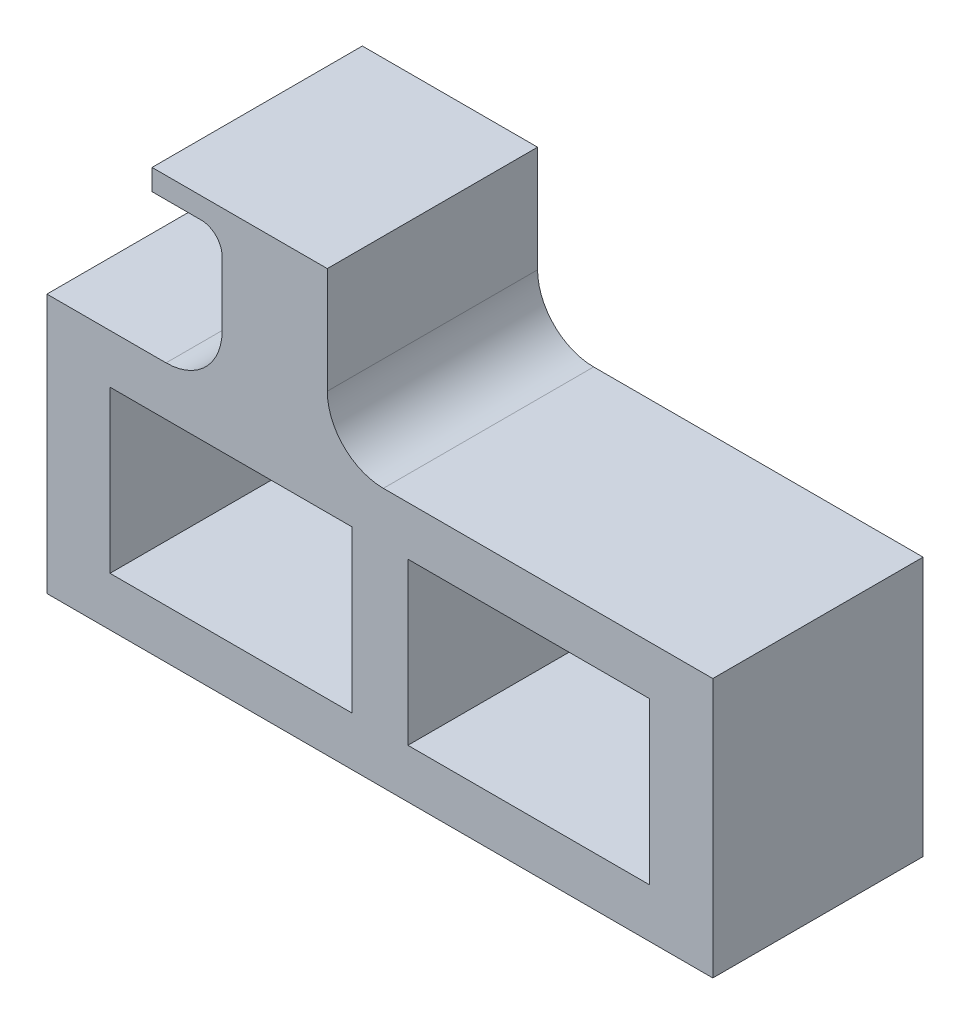
SolidWorks part; units mm, degrees
ref_plane "Front Plane" through (0, 0, 0) normal (0, 0, 1) x (1, 0, 0)
ref_plane "Top Plane" through (0, 0, 0) normal (0, 1, 0) x (1, 0, 0)
ref_plane "Right Plane" through (0, 0, 0) normal (1, 0, 0) x (0, 0, -1)
sketch "Sketch1" plane through (0, 0, 0) normal (0, 1, 0) x (1, 0, 0)
  line L1 (0, 0) -> (95, 0)
  line L2 (0, 0) -> (0, 30)
  line L3 (0, 30) -> (95, 30)
  line L4 (95, 0) -> (95, 30)
  dimension "D1" = 95
  dimension "D2" = 30
extrude "Boss-Extrude1" add sketch "Sketch1" along normal blind 7 contours L1 L4 L3 L2
sketch "Sketch2" plane through (0, 7, 0) normal (0, 1, 0) x (1, 0, 0)
  line L0 (0, 30) -> (95, 30) construction
  line L1 (0, 0) -> (9, 0)
  line L2 (0, 0) -> (0, 30)
  line L3 (0, 30) -> (9, 30)
  line L4 (9, 0) -> (9, 30)
  line L5 (47.5, 0) -> (47.5, 30) construction
  line L6 (0, 0) -> (95, 0) construction
  line L7 (51.5, 30) -> (51.5, 0)
  line L8 (51.5, 30) -> (43.5, 30)
  line L9 (47.5, 30) -> (47.5, 0)
  line L10 (51.5, 0) -> (43.5, 0)
  line L11 (43.5, 30) -> (43.5, 0)
  line L12 (95, 30) -> (86, 30)
  line L13 (95, 0) -> (86, 0)
  line L14 (95, 0) -> (95, 30)
  line L15 (86, 0) -> (86, 30)
  line M9 (0, 30) -> (0, 0)
  line M10 (0, 0) -> (95, 0)
  line M11 (95, 0) -> (95, 30)
  line M12 (95, 30) -> (0, 30)
  dimension "D1" = 9
  dimension "D2" = 4
extrude "Boss-Extrude2" add sketch "Sketch2" along normal blind 23 contours L4 M10 M12 M9 | L8 L11 L9 M10 | L9 L7 M12 M10 | L15 M10 M11 M12 region at (4.5, 7, -15) region at (45.5, 7, -15) region at (49.5, 7, -15) region at (90.5, 7, -15)
sketch "Sketch3" plane through (0, 30, 0) normal (0, 1, 0) x (1, 0, 0)
  line L1 (0, 0) -> (95, 0)
  line L2 (0, 0) -> (0, 30)
  line L3 (0, 30) -> (95, 30)
  line L4 (95, 0) -> (95, 30)
extrude "Boss-Extrude3" add sketch "Sketch3" along normal blind 7
sketch "Sketch4" plane through (0, 37, 0) normal (0, 1, 0) x (1, 0, 0)
  line L0 (0, 30) -> (0, 0) construction
  line L1 (25, 0) -> (40, 0)
  line L2 (25, 0) -> (25, 30)
  line L3 (25, 30) -> (40, 30)
  line L4 (40, 0) -> (40, 30)
  line L5 (0, 0) -> (95, 0) construction
  line L6 (95, 30) -> (0, 30) construction
  dimension "D1" = 25
  dimension "D2" = 15
extrude "Boss-Extrude4" add sketch "Sketch4" along normal blind 20.15
sketch "Sketch5" plane through (0, 57.15, 0) normal (0, 1, 0) x (1, 0, 0)
  line L0 (40, 0) -> (40, 30) construction
  line L1 (15, 30) -> (40, 30)
  line L2 (15, 30) -> (15, 0)
  line L3 (15, 0) -> (40, 0)
  line L4 (40, 30) -> (40, 0)
  line L5 (25, 0) -> (40, 0) construction
  line L6 (40, 30) -> (25, 30) construction
  point P5 (0, 0)
  dimension "D2" = 25
extrude "Boss-Extrude5" add sketch "Sketch5" along normal blind 3
fillet "Fillet2" radius 3 1 edges at (25, 57.15, -15)
fillet "Fillet3" radius 8 2 edges at (40, 37, -15) (25, 37, -15)
